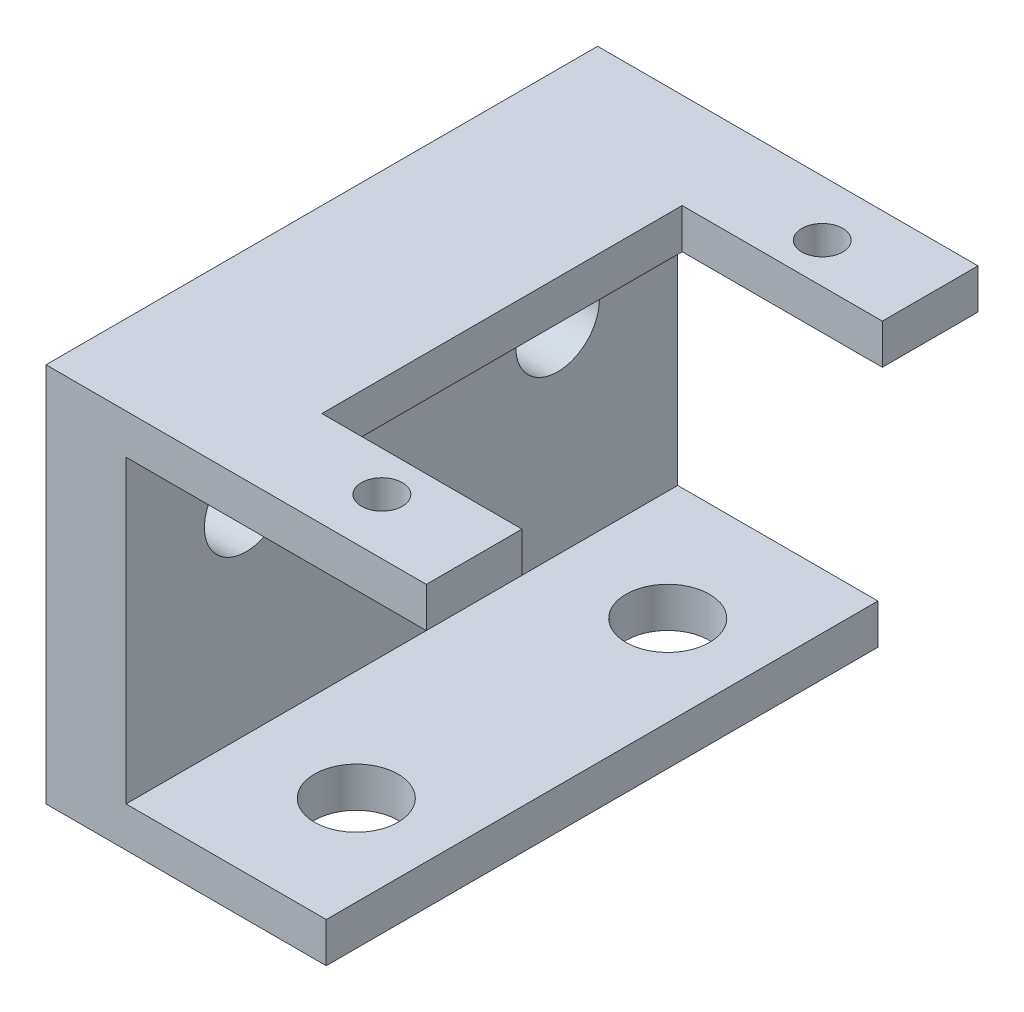
SolidWorks part; units mm, degrees
ref_plane "Front Plane" through (0, 0, 0) normal (0, 0, 1) x (1, 0, 0)
ref_plane "Top Plane" through (0, 0, 0) normal (0, 1, 0) x (1, 0, 0)
ref_plane "Right Plane" through (0, 0, 0) normal (1, 0, 0) x (0, 0, -1)
sketch "Sketch1" plane through (0, 0, 0) normal (0, 0, 1) x (1, 0, 0)
  line L1 (0, 0) -> (17.78, 0)
  line L2 (0, 0) -> (0, 2.54)
  line L3 (0, 2.54) -> (17.78, 2.54)
  line L4 (17.78, 0) -> (17.78, 2.54)
  line L5 (0, 2.54) -> (5.08, 2.54)
  line L6 (0, 2.54) -> (0, 21.59)
  line L7 (0, 21.59) -> (5.08, 21.59)
  line L8 (5.08, 2.54) -> (5.08, 21.59)
  line L9 (0, 21.59) -> (24.13, 21.59)
  line L10 (0, 21.59) -> (0, 24.13)
  line L11 (0, 24.13) -> (24.13, 24.13)
  line L12 (24.13, 21.59) -> (24.13, 24.13)
  dimension "D1" = 5.08
  dimension "D2" = 12.7
  dimension "D3" = 19.05
  dimension "D4" = 2.54
  dimension "D5" = 2.54
  dimension "D6" = 19.05
extrude "Boss-Extrude1" add sketch "Sketch1" along normal blind 35 contours L9 L12 L11 L10 L7 | L6 L5 L8 L7 | L2 L1 L4 L3 region at (12.065, 22.86, 0)
hole_wizard "Ø5.0mm Dowel Hole1" positions "Sketch2" profile "Sketch3" hole size "Ø5.0" standard "ANSI Metric" end condition through all
sketch "Sketch2" plane through (5.08, 0, 0) normal (1, 0, 0) x (0, 0, -1)
  line L3 (-35, 2.54) -> (0, 2.54) construction
  line L4 (-35, 2.54) -> (-35, 21.59) construction
  line L5 (0, 2.54) -> (0, 21.59) construction
  point P0 (-27.38, 15.24)
  point P2 (-7.62, 15.24)
  dimension "D1" = 7.62
  dimension "D2" = 7.62
  dimension "D3" = 12.7
sketch "Sketch3" plane through (5.08, 15.24, 27.38) normal (0, 1, 0) x (0, 0, -1)
  line L0 (0, 0) -> (0, 5.08)
  line L1 (0, 5.08) -> (2.65, 5.08)
  line L2 (2.65, 5.08) -> (2.65, 0)
  line L5 (2.65, 0) -> (0, 0)
  line L11 (0, -6.35) -> (0, 107.95) construction
  dimension "Thru Hole Dia." = 5.3
  dimension "Thru Hole Depth" = 5.08
hole_wizard "Ø5.0mm Dowel Hole2" positions "Sketch4" profile "Sketch5" hole size "Ø5.0" standard "ANSI Metric" end condition through all
sketch "Sketch4" plane through (0, 2.54, 0) normal (0, 1, 0) x (1, 0, 0)
  line L2 (12.065, 0) -> (12.065, -35) construction
  line L3 (0, 0) -> (24.13, 0) construction
  line L4 (0, -35) -> (24.13, -35) construction
  point P0 (12.065, -27.38)
  point P2 (12.065, -7.62)
  point P16 (12.065, 0)
  point P18 (12.065, -35)
  dimension "D1" = 7.62
  dimension "D2" = 7.62
sketch "Sketch5" plane through (12.065, 2.54, 27.38) normal (1, 0, 0) x (0, 0, 1)
  line L0 (0, 0) -> (0, 2.54)
  line L1 (0, 2.54) -> (2.65, 2.54)
  line L2 (2.65, 2.54) -> (2.65, 0)
  line L5 (2.65, 0) -> (0, 0)
  line L11 (0, -6.35) -> (0, 107.95) construction
  dimension "Thru Hole Dia." = 5.3
  dimension "Thru Hole Depth" = 2.54
sketch "Sketch6" plane through (0, 24.13, 0) normal (0, 1, 0) x (1, 0, 0)
  line L0 (24.13, -35) -> (24.13, 0) construction
  line L1 (24.13, -6.07) -> (11.43, -6.07)
  line L2 (24.13, -6.07) -> (24.13, -28.93)
  line L3 (24.13, -28.93) -> (11.43, -28.93)
  line L4 (11.43, -6.07) -> (11.43, -28.93)
  line L5 (0, 0) -> (24.13, 0) construction
  line L6 (0, -35) -> (24.13, -35) construction
  line L9 (17.78, -6.07) -> (17.78, 0) construction
  line L10 (17.78, -28.93) -> (17.78, -35) construction
  dimension "D2" = 12.7
  dimension "D1" = 22.86
extrude "Cut-Extrude1" cut sketch "Sketch6" against normal up to next contours L2 L1 L4 L3
hole_wizard "M2 Clearance Hole1" positions "Sketch7" profile "Sketch8" hole size "M2" standard "ANSI Metric" end condition up to next
sketch "Sketch7" plane through (0, 24.13, 0) normal (0, 1, 0) x (1, 0, 0)
  line L0 (17.78, -28.93) -> (17.78, -35) construction
  line L1 (17.78, -6.07) -> (17.78, 0) construction
  line L2 (11.43, -6.07) -> (11.43, -28.93) construction
  point P0 (17.78, -31.47)
  point P4 (17.78, -3.53)
  point P13 (11.43, -17.5)
  dimension "D1" = 13.97
  dimension "D2" = 13.97
sketch "Sketch8" plane through (17.78, 24.13, 31.47) normal (1, 0, 0) x (0, 0, 1)
  line L0 (0, 0) -> (0, 2.54)
  line L1 (0, 2.54) -> (1.3, 2.54)
  line L2 (1.3, 2.54) -> (1.3, 0)
  line L5 (1.3, 0) -> (0, 0)
  line L11 (0, -6.35) -> (0, 107.95) construction
  dimension "Thru Hole Dia." = 2.6
  dimension "Thru Hole Depth" = 2.54
equation "\"wall thicc\"= 2.5mm"
equation "\"press fit\"= 0.3mm"
equation "\"shaft thick\"= 5mm + \"press fit\""
equation "\"D1@Sketch1\"=\"wall thicc\"*2"
equation "\"D4@Sketch1\"=\"wall thicc\""
equation "\"D5@Sketch1\"=\"wall thicc\""
equation "\"servo width\"= 22.5mm"
equation "\"D1@Sketch6\"=\"servo width\"+\"press fit\""
equation "\"servo length\"= 12.5mm"
equation "\"D2@Sketch6\"=\"servo length\"+\"press fit\""
equation "\"servo hole spacing\"= 13.9mm"
equation "\"D1@Sketch7\"=\"servo hole spacing\""
equation "\"D2@Sketch7\"=\"servo hole spacing\""
